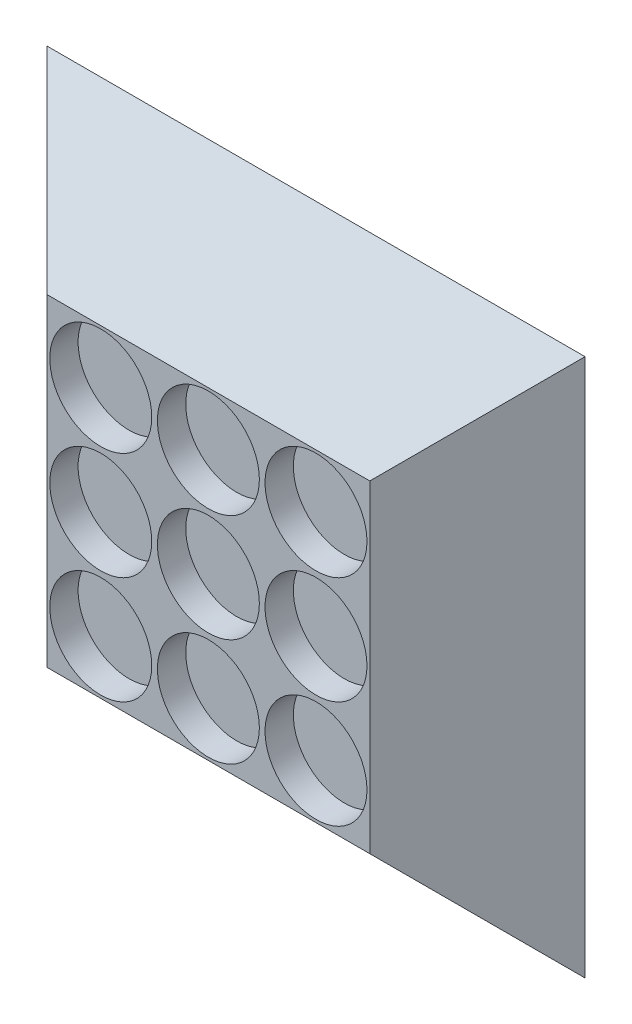
SolidWorks part; units mm, degrees
ref_plane "Спереди" through (0, 0, 0) normal (0, 0, 1) x (1, 0, 0)
ref_plane "Сверху" through (0, 0, 0) normal (0, 1, 0) x (1, 0, 0)
ref_plane "Справа" through (0, 0, 0) normal (1, 0, 0) x (0, 0, -1)
sketch "Эскиз1" plane through (0, 0, 0) normal (0, 0, 1) x (1, 0, 0)
  line L1 (47.5, -47.5) -> (-47.5, -47.5)
  line L2 (47.5, -47.5) -> (47.5, 47.5)
  line L3 (47.5, 47.5) -> (-47.5, 47.5)
  line L4 (-47.5, -47.5) -> (-47.5, 47.5)
  line L5 (47.5, -47.5) -> (-47.5, 47.5) construction
  line L6 (47.5, 47.5) -> (-47.5, -47.5) construction
  point P0 (0, 0)
  dimension "D1" = 95
extrude "Бобышка-Вытянуть1" add sketch "Эскиз1" along normal blind 19
chamfer "Фаска1" distance 19 angle 45 4 edges at (0, 47.5, 19) (47.5, 0, 19) (0, -47.5, 19) (-47.5, 0, 19)
sketch "Эскиз2" plane through (0, 0, 19) normal (0, 0, 1) x (1, 0, 0)
  line L0 (0, 0) -> (19, 0) construction
  line L1 (0, 0) -> (0, 19) construction
  line L2 (0, 19) -> (-19, 19) construction
  line L3 (-19, 0) -> (-19, -19) construction
  circle A0 centre (0, 0) radius 9
  circle A1 centre (19, 0) radius 9
  circle A2 centre (19, 19) radius 9
  circle A3 centre (0, 19) radius 9
  circle A4 centre (-19, 19) radius 9
  circle A5 centre (-19, 0) radius 9
  circle A6 centre (-19, -19) radius 9
  circle A7 centre (0, -19) radius 9
  circle A8 centre (19, -19) radius 9
  dimension "D1" = 18
  dimension "D4" = 19
  dimension "D5" = 19
  dimension "D7" = 19
  dimension "D9" = 19
  dimension "D2" = 2
  dimension "D3" = 2
  dimension "D6" = 2
  dimension "D8" = 2
extrude "Вырез-Вытянуть1" cut sketch "Эскиз2" against normal blind 5
equation "\"D1@Эскиз1\"=19*3+19*2"
